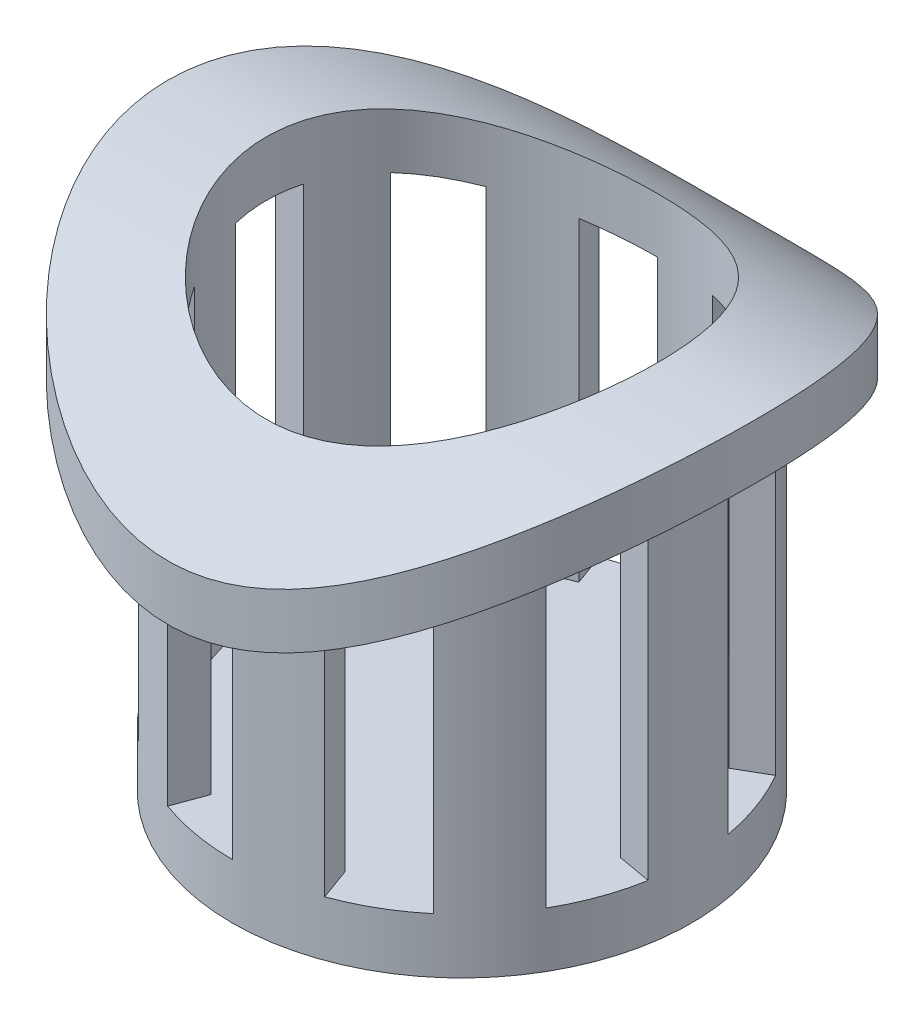
SolidWorks part; units mm, degrees
ref_plane "Front Plane" through (0, 0, 0) normal (0, 0, 1) x (1, 0, 0)
ref_plane "Top Plane" through (0, 0, 0) normal (0, 1, 0) x (1, 0, 0)
ref_plane "Right Plane" through (0, 0, 0) normal (1, 0, 0) x (0, 0, -1)
sketch "Sketch1" plane through (0, 0, 0) normal (0, 1, 0) x (1, 0, 0)
  circle A0 centre (0, 0) radius 27.051
  circle A1 centre (0, 0) radius 40.64
  dimension "D1" = 54.102
  dimension "D2" = 81.28
extrude "Boss-Extrude1" add sketch "Sketch1" along normal blind 101.6
sketch "Sketch2" plane through (0, 0, 0) normal (1, 0, 0) x (0, 0, -1)
  circle A0 centre (0, 0) radius 57.15
  dimension "D1" = 114.3
extrude "Cut-Extrude1" cut sketch "Sketch2" against normal blind 101.6 and the other way blind 101.6
sketch "Sketch5" plane through (0, 0, 0) normal (0, 1, 0) x (1, 0, 0)
  circle A0 centre (0, 0) radius 31.75
  dimension "D1" = 63.5
extrude "Boss-Extrude2" add sketch "Sketch5" along normal blind 7.62 separate body
sketch "Sketch11" plane through (0, 7.62, 0) normal (0, 1, 0) x (1, 0, 0)
  line L0 (23.4269, -13.5255) -> (27.4963, -15.875)
  line L1 (26.64, 4.6974) -> (31.2676, 5.5133)
  line L2 (26.64, -4.6974) -> (31.2676, -5.5133)
  line L3 (17.388, -20.7223) -> (20.4085, -24.3219)
  line L4 (9.252, -25.4196) -> (10.8591, -29.8352)
  line L5 (0, -27.051) -> (0, -31.75)
  line L6 (-9.252, -25.4196) -> (-10.8591, -29.8352)
  line L7 (-17.388, -20.7223) -> (-20.4085, -24.3219)
  line L8 (-23.4269, -13.5255) -> (-27.4963, -15.875)
  line L9 (-26.64, -4.6974) -> (-31.2676, -5.5133)
  line L10 (-26.64, 4.6974) -> (-31.2676, 5.5133)
  line L11 (-23.4269, 13.5255) -> (-27.4963, 15.875)
  line L12 (-17.388, 20.7223) -> (-20.4085, 24.3219)
  line L13 (-9.252, 25.4196) -> (-10.8591, 29.8352)
  line L14 (0, 27.051) -> (0, 31.75)
  line L15 (9.252, 25.4196) -> (10.8591, 29.8352)
  line L16 (17.388, 20.7223) -> (20.4085, 24.3219)
  line L17 (23.4269, 13.5255) -> (27.4963, 15.875)
  arc A0 (31.2676, -5.5133) -> (31.2676, 5.5133) centre (0, 0) ccw
  arc A1 (26.64, -4.6974) -> (26.64, 4.6974) centre (0, 0) ccw
  arc A2 (20.4085, -24.3219) -> (27.4963, -15.875) centre (0, 0) ccw
  arc A3 (17.388, -20.7223) -> (23.4269, -13.5255) centre (0, 0) ccw
  arc A4 (0, -31.75) -> (10.8591, -29.8352) centre (0, 0) ccw
  arc A5 (0, -27.051) -> (9.252, -25.4196) centre (0, 0) ccw
  arc A6 (-20.4085, -24.3219) -> (-10.8591, -29.8352) centre (0, 0) ccw
  arc A7 (-17.388, -20.7223) -> (-9.252, -25.4196) centre (0, 0) ccw
  arc A8 (-31.2676, -5.5133) -> (-27.4963, -15.875) centre (0, 0) ccw
  arc A9 (-26.64, -4.6974) -> (-23.4269, -13.5255) centre (0, 0) ccw
  arc A10 (-27.4963, 15.875) -> (-31.2676, 5.5133) centre (0, 0) ccw
  arc A11 (-23.4269, 13.5255) -> (-26.64, 4.6974) centre (0, 0) ccw
  arc A12 (-10.8591, 29.8352) -> (-20.4085, 24.3219) centre (0, 0) ccw
  arc A13 (-9.252, 25.4196) -> (-17.388, 20.7223) centre (0, 0) ccw
  arc A14 (10.8591, 29.8352) -> (0, 31.75) centre (0, 0) ccw
  arc A15 (9.252, 25.4196) -> (0, 27.051) centre (0, 0) ccw
  arc A16 (27.4963, 15.875) -> (20.4085, 24.3219) centre (0, 0) ccw
  arc A17 (23.4269, 13.5255) -> (17.388, 20.7223) centre (0, 0) ccw
  point P41 (0, 0)
  dimension "D1" = 54.102
  dimension "D2" = 9
extrude "Boss-Extrude6" add sketch "Sketch11" along normal blind 50.8
sketch "Sketch4" plane through (0, 0, 0) normal (1, 0, 0) x (0, 0, -1)
  circle A0 centre (0, 7.62) radius 57.15
  circle A1 centre (0, 0) radius 120.6658
  dimension "D1" = 114.3
  dimension "D2" = 7.62
extrude "Cut-Extrude2" cut sketch "Sketch4" against normal blind 101.6 and the other way blind 101.6
